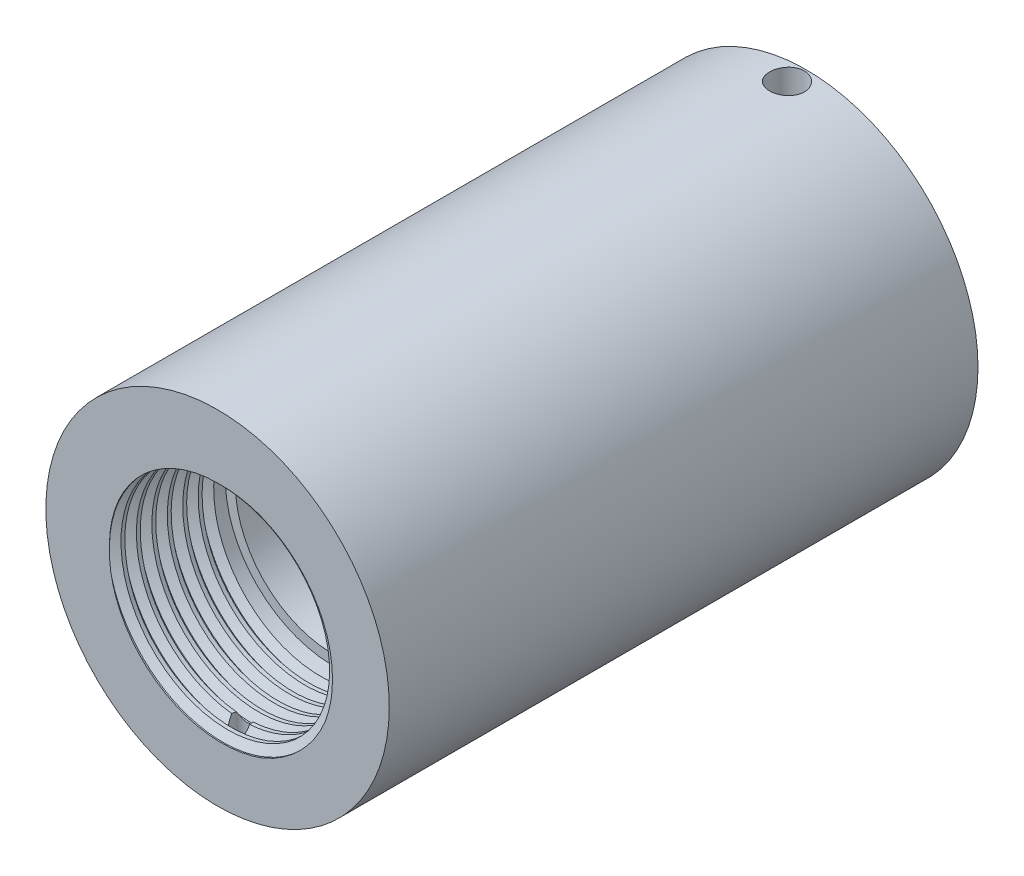
SolidWorks part; units mm, degrees
ref_plane "Front Plane" through (0, 0, 0) normal (0, 0, 1) x (1, 0, 0)
ref_plane "Top Plane" through (0, 0, 0) normal (0, 1, 0) x (1, 0, 0)
ref_plane "Right Plane" through (0, 0, 0) normal (1, 0, 0) x (0, 0, -1)
sketch "Sketch1" plane through (0, 0, 0) normal (0, 0, 1) x (1, 0, 0)
  circle A0 centre (0, 0) radius 22.225
  circle A1 centre (0, 0) radius 12.7
  dimension "D1" = 44.45
  dimension "D2" = 25.4
extrude "Boss-Extrude1" add sketch "Sketch1" along normal blind 76.2
sketch "Sketch2" plane through (0, 0, 0) normal (0, 0, -1) x (-1, 0, 0)
  circle A0 centre (0, 0) radius 18
  dimension "D1" = 36
extrude "Cut-Extrude1" cut sketch "Sketch2" against normal blind 20
hole_wizard "M4 Clearance Hole1" positions "3DSketch1" profile "Sketch3" hole size "M4" standard "ANSI Metric" end condition through all
sketch3d "3DSketch1"
  line L0 (0, 22.225, 2.5) -> (0, 22.225, 0) construction
  circle A0 centre (0, 0, 0) radius 22.225 construction
  point P0 (0, 22.225, 2.5)
  point P6 (0, 0, 22.225)
  dimension "D1" = 2.5
sketch "Sketch3" plane through (0, 22.225, 2.5) normal (1, 0, 0) x (0, 0, 1)
  line L0 (0, 0) -> (0, 44.45)
  line L1 (0, 44.45) -> (2.25, 44.45)
  line L2 (2.25, 44.45) -> (2.25, 0)
  line L5 (2.25, 0) -> (0, 0)
  line L11 (0, -6.35) -> (0, 107.95) construction
  dimension "Thru Hole Dia." = 4.5
  dimension "Thru Hole Depth" = 44.45
sketch "Sketch4" plane through (0, 0, 76.2) normal (0, 0, 1) x (1, 0, 0)
  circle A0 centre (0, 0) radius 14
  dimension "D1" = 28
extrude "Cut-Extrude2" cut sketch "Sketch4" against normal blind 15
thread "Thread1" pitch 2 method cut profile "Thread Profile2" start angle 0, offset 2, length 15, pitch 2, diameter 28
ref_plane "Plane2" through (-14, 0, 78.2) normal (0, -1, 0) x (-1, 0, 0)
sketch "Thread Profile2" plane through (-14, 0, 78.2) normal (0, -1, 0) x (-1, 0, 0)
  line L0 (0, 0) -> (0, 2) construction
  line L1 (0, 0) -> (1.0825, 0.625)
  line L2 (1.0825, 0.625) -> (1.0825, 0.875)
  line L3 (1.0825, 0.875) -> (0, 1.5)
  line L4 (1.0825, 0.75) -> (0, 0.75) construction
  line L11 (0, 0) -> (0, 1.5)
  point P2 (0, 0)
  dimension "Pitch" = 2
  dimension "Profile_Angle" = 60
  dimension "Profile_Land" = 0.25
  dimension "Profile_Height" = 1.0825
hole_wizard "3/32 (0.09375) Diameter Hole1" positions "3DSketch2" profile "Sketch12" hole size "3/32" standard "ANSI Inch" end condition up to next
sketch3d "3DSketch2"
  line L0 (0, -22.225, 73.2) -> (0, -22.225, 76.2) construction
  circle A0 centre (0, 0, 76.2) radius 22.225 construction
  point P0 (0, -22.225, 73.2)
  point P8 (0, 0, 98.425)
  dimension "D1" = 3
sketch "Sketch12" plane through (0, -22.225, 73.2) normal (1, 0, 0) x (0, 0, -1)
  line L0 (0, 0) -> (0, 8.225)
  line L1 (0, 8.225) -> (1.1906, 8.225)
  line L2 (1.1906, 8.225) -> (1.1906, 0)
  line L5 (1.1906, 0) -> (0, 0)
  line L11 (0, -6.35) -> (0, 107.95) construction
  dimension "Thru Hole Dia." = 2.3812
  dimension "Thru Hole Depth" = 8.225
